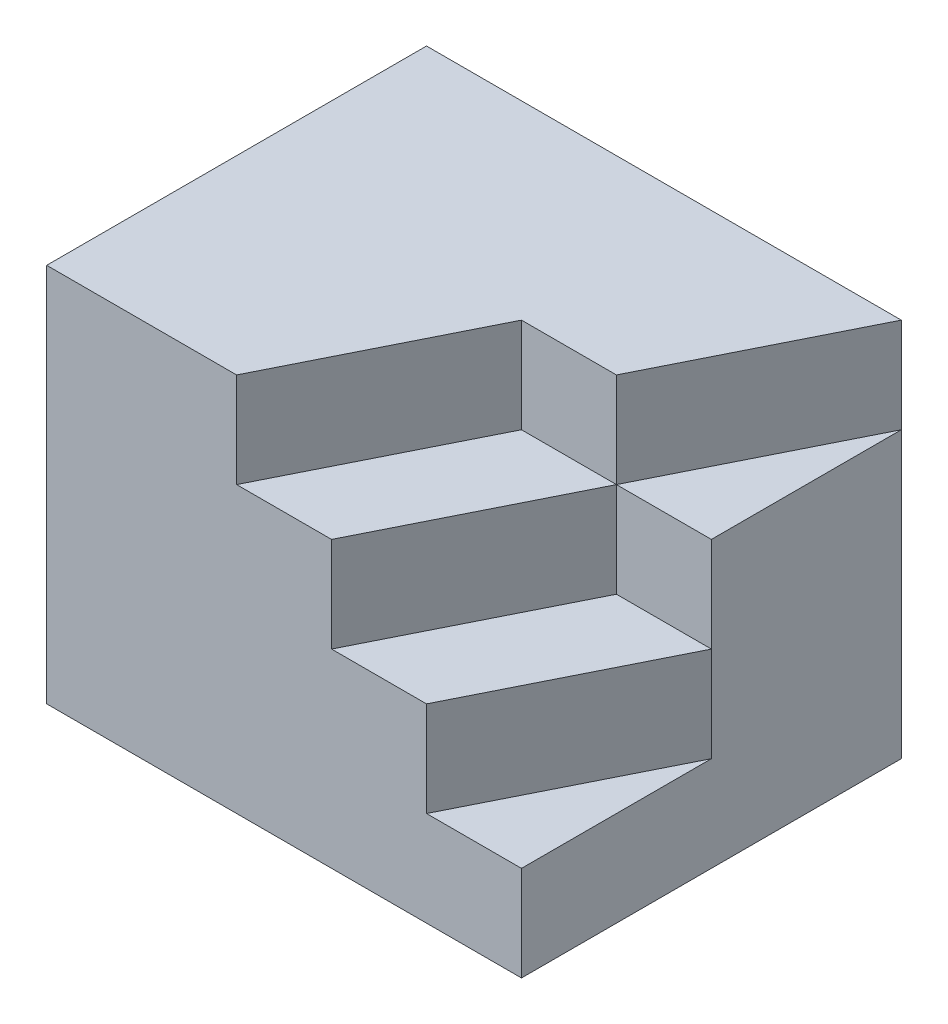
SolidWorks part; units mm, degrees
ref_plane "前基準面" through (0, 0, 0) normal (0, 0, 1) x (1, 0, 0)
ref_plane "上基準面" through (0, 0, 0) normal (0, 1, 0) x (1, 0, 0)
ref_plane "右基準面" through (0, 0, 0) normal (1, 0, 0) x (0, 0, -1)
sketch "草圖1" plane through (0, 0, 0) normal (0, 0, 1) x (1, 0, 0)
  line L1 (25, 20) -> (0, 20)
  line L2 (25, 20) -> (25, 0)
  line L3 (25, 0) -> (0, 0)
  line L4 (0, 20) -> (0, 0)
  dimension "D1" = 25
  dimension "D2" = 20
extrude "填料-伸長1" add sketch "草圖1" against normal blind 20
sketch "草圖2" plane through (0, 20, 0) normal (0, 1, 0) x (1, 0, 0)
  line L0 (10, 0) -> (15, 10)
  line L1 (10, 0) -> (15, 0)
  line L2 (15, 10) -> (20, 10)
  line L3 (15, 0) -> (20, 10)
  line L4 (25, 0) -> (0, 0) construction
  line L5 (25, 20) -> (25, 0) construction
  dimension "D1" = 5
  dimension "D2" = 10
  dimension "D3" = 5
  dimension "D4" = 10
extrude "除料-伸長1" cut sketch "草圖2" against normal blind 5
sketch "草圖4" plane through (0, 20, 0) normal (0, 1, 0) x (1, 0, 0)
  line L0 (25, 0) -> (25, 20)
  line L1 (25, 20) -> (15, 0)
  line L2 (15, 0) -> (25, 0)
extrude "除料-伸長8" cut sketch "草圖4" against normal blind 5 contours L2 L0 L1
sketch "草圖6" plane through (0, 15, 0) normal (0, 1, 0) x (1, 0, 0)
  line L0 (15, 0) -> (20, 10)
  line L1 (15, 0) -> (25, 0)
  line L2 (20, 10) -> (25, 10)
  line L3 (25, 10) -> (25, 0)
  line L6 (10, 0) -> (25, 0) construction
  line L7 (15, 10) -> (10, 0) construction
  line L8 (20, 10) -> (15, 10) construction
  point P8 (24.6356, 0)
  dimension "D1" = 5
extrude "除料-伸長11" cut sketch "草圖6" against normal blind 5
sketch "草圖8" plane through (0, 10, 0) normal (0, 1, 0) x (1, 0, 0)
  line L0 (25, 10) -> (25, 0)
  line L1 (25, 0) -> (20, 0)
  line L2 (15, 0) -> (25, 0) construction
  line L3 (20, 0) -> (25, 10)
  line L4 (20, 10) -> (15, 0) construction
extrude "除料-伸長12" cut sketch "草圖8" against normal blind 5
